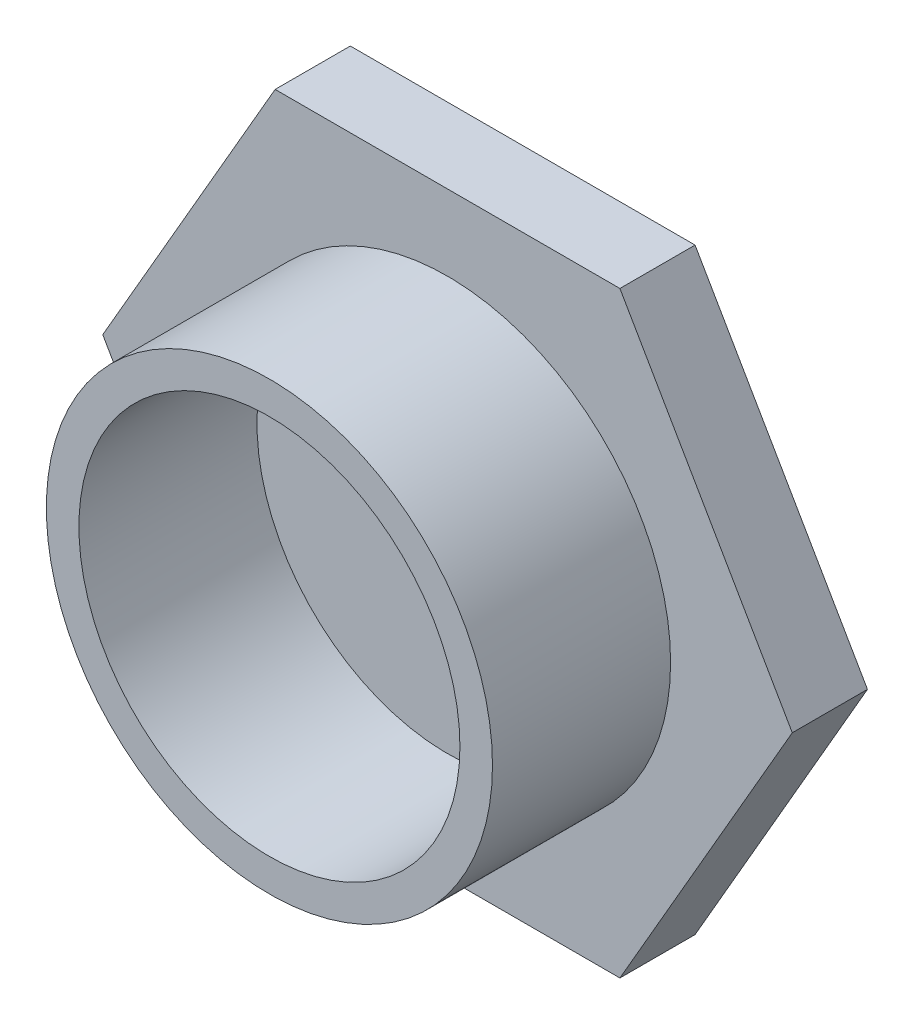
SolidWorks part; units mm, degrees
ref_plane "Front Plane" through (0, 0, 0) normal (0, 0, 1) x (1, 0, 0)
ref_plane "Top Plane" through (0, 0, 0) normal (0, 1, 0) x (1, 0, 0)
ref_plane "Right Plane" through (0, 0, 0) normal (1, 0, 0) x (0, 0, -1)
sketch "Sketch1" plane through (0, 0, 0) normal (0, 0, 1) x (1, 0, 0)
  line L1 (12.465, 21.59) -> (-12.465, 21.59)
  line L2 (-12.465, 21.59) -> (-24.93, 0)
  line L3 (-24.93, 0) -> (-12.465, -21.59)
  line L4 (-12.465, -21.59) -> (12.465, -21.59)
  line L5 (12.465, -21.59) -> (24.93, 0)
  line L6 (24.93, 0) -> (12.465, 21.59)
  circle A0 centre (0, 0) radius 21.59 construction
  circle A1 centre (0, 0) radius 16.1299
  circle A2 centre (0, 0) radius 13.7761
  dimension "D2" = 32.2598
  dimension "D3" = 27.5521
  dimension "D1" = 43.18
extrude "Boss-Extrude1" add sketch "Sketch1" along normal blind 5.4356 contours L2 L3 L4 L5 L6 L1
extrude "Boss-Extrude2" add sketch "Sketch1<3>" along normal blind 12.8778 from surface contours A1 A2 region at (-15.6737, 0, 0) starting at face at (0, 0, 5.4356)
sketch "Sketch1<3>" plane through (0, 0, 0) normal (0, 0, 1) x (1, 0, 0) same geometry as "Sketch1"
